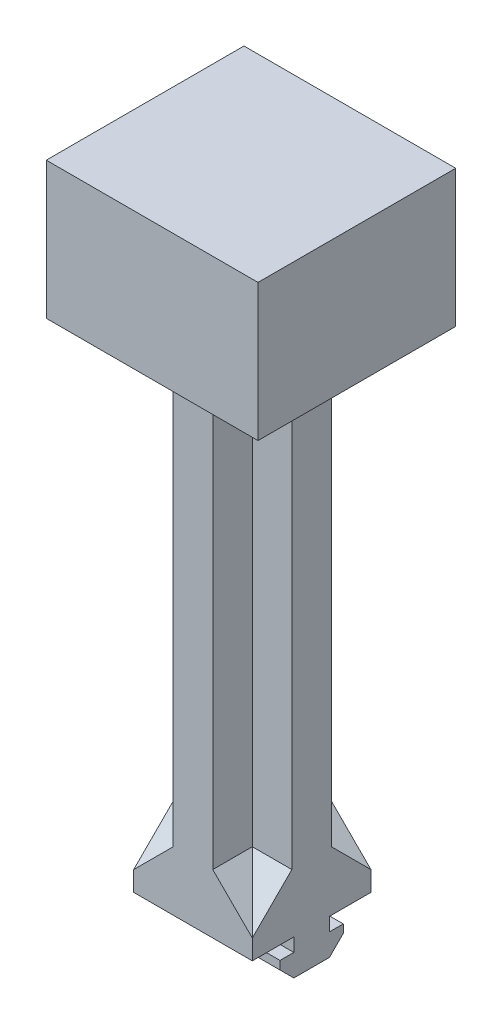
SolidWorks part; units mm, degrees
ref_plane "Front Plane" through (0, 0, 0) normal (0, 0, 1) x (1, 0, 0)
ref_plane "Top Plane" through (0, 0, 0) normal (0, 1, 0) x (1, 0, 0)
ref_plane "Right Plane" through (0, 0, 0) normal (1, 0, 0) x (0, 0, -1)
sketch "Sketch1" plane through (0, 0, 0) normal (0, 0, 1) x (1, 0, 0)
  line L1 (0, 0) -> (34, 0)
  line L2 (0, 0) -> (0, 22)
  line L3 (0, 22) -> (34, 22)
  line L4 (34, 0) -> (34, 22)
  dimension "D1" = 34
  dimension "D2" = 22
extrude "Boss-Extrude1" add sketch "Sketch1" along normal blind 31.75
shell "Shell1" thickness 3.5 removed face at (17, 11, 0)
sketch "Sketch2" plane through (0, 0, 0) normal (0, -1, 0) x (1, 0, 0)
  line L0 (13.825, 25.1899) -> (13.825, 18.8399)
  line L4 (13.825, 18.8399) -> (7.475, 18.8399)
  line L5 (7.475, 18.8399) -> (7.475, 12.4899)
  line L6 (7.475, 12.4899) -> (13.825, 12.4899)
  line L7 (13.825, 12.4899) -> (13.825, 6.1399)
  line L13 (13.825, 6.1399) -> (20.175, 6.1399)
  line L14 (20.175, 6.1399) -> (20.175, 12.4899)
  line L15 (20.175, 12.4899) -> (26.525, 12.4899)
  line L16 (26.525, 12.4899) -> (26.525, 18.8399)
  line L17 (26.525, 18.8399) -> (20.175, 18.8399)
  line L18 (20.175, 18.8399) -> (20.175, 25.1899)
  line L19 (20.175, 25.1899) -> (13.825, 25.1899)
  line L20 (0, 31.75) -> (34, 0) construction
  line L21 (0, 0) -> (34, 31.75) construction
  dimension "D1" = 6.35
extrude "Boss-Extrude2" add sketch "Sketch2" along normal blind 76.2
sketch "Sketch3" plane through (0, 0, 0) normal (1, 0, 0) x (0, 0, -1)
  line L5 (-10.5849, -81.534) -> (-10.5849, -82.8675)
  line L6 (-10.5849, -82.8675) -> (-12.8074, -85.09)
  line L7 (-12.8074, -85.09) -> (-18.5224, -85.09)
  line L8 (-18.5224, -85.09) -> (-20.7449, -82.8675)
  line L9 (-20.7449, -82.8675) -> (-20.7449, -81.534)
  line L14 (-6.1399, -76.2) -> (-25.1899, -76.2)
  line L15 (-25.1899, -76.2) -> (-25.1899, -79.375)
  line L16 (-25.1899, -79.375) -> (-18.5224, -79.375)
  line L17 (-18.5224, -79.375) -> (-18.5224, -81.534)
  line L18 (-18.5224, -81.534) -> (-20.7449, -81.534)
  line L19 (-12.8074, -79.375) -> (-12.8074, -81.534)
  line L20 (-12.8074, -81.534) -> (-10.5849, -81.534)
  line L21 (-6.1399, -76.2) -> (-6.1399, -79.375)
  line L22 (-12.8074, -79.375) -> (-6.1399, -79.375)
  line L23 (-25.1899, -76.2) -> (-25.1899, 0) construction
  line L24 (-18.8399, -76.2) -> (-25.1899, -76.2) construction
  line L26 (-6.1399, -76.2) -> (-6.1399, 0) construction
  dimension "D1" = 5.715
  dimension "D3" = 10.16
  dimension "D4" = 2.159
  dimension "D5" = 5.715
  dimension "D6" = 3.175
extrude "Boss-Extrude3" add sketch "Sketch3" against normal up to surface (-7.475 mm away) from surface up to face at (7.475, -38.1, 15.6649) starting at face at (26.525, -38.1, 15.6649)
chamfer "Chamfer1" distance 6.35 angle 45 16 edges at (10.65, -76.2, 18.8399) (13.825, -76.2, 22.0149) (23.35, -76.2, 18.8399) (20.175, -76.2, 22.0149) (23.35, -76.2, 12.4899) (20.175, -76.2, 9.3149) (10.65, -76.2, 12.4899) (13.825, -76.2, 9.3149) (13.825, 0, 22.0149) (10.65, 0, 18.8399) (23.35, 0, 18.8399) (20.175, 0, 22.0149) (20.175, 0, 9.3149) (23.35, 0, 12.4899) (13.825, 0, 9.3149) (10.65, 0, 12.4899)
